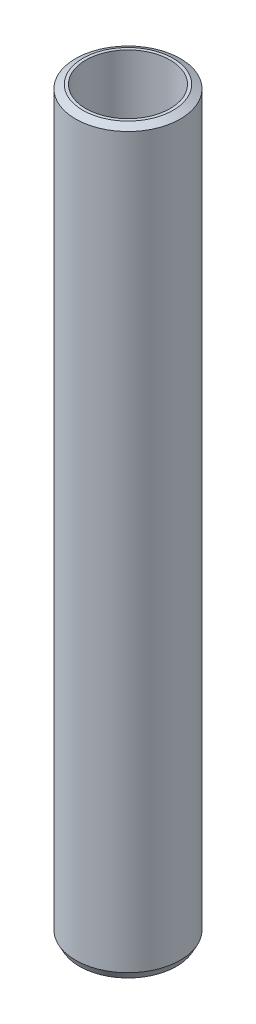
SolidWorks part; units mm, degrees
ref_plane "Front Plane" through (0, 0, 0) normal (0, 0, 1) x (1, 0, 0)
ref_plane "Top Plane" through (0, 0, 0) normal (0, 1, 0) x (1, 0, 0)
ref_plane "Right Plane" through (0, 0, 0) normal (1, 0, 0) x (0, 0, -1)
sketch "Sketch1" plane through (0, 0, 0) normal (0, 1, 0) x (1, 0, 0)
  circle A0 centre (0, 0) radius 42.5
  dimension "SHAFT_OD" = 85
extrude "Boss-Extrude1" add sketch "Sketch1" along normal blind 600
sketch "Sketch2" plane through (0, 0, 0) normal (0, 1, 0) x (1, 0, 0)
  circle A0 centre (0, 0) radius 34.1786
  dimension "BORE_D" = 68.3572
extrude "Cut-Extrude1" cut sketch "Sketch2" along normal through all
chamfer "Chamfer1" distance 3.1424 angle 62.032 2 edges at (0, 600, 42.5) (0, 0, 42.5) first distance on face at (0, 600, 42.5) first distance on face at (0, 0, 34.1786)
